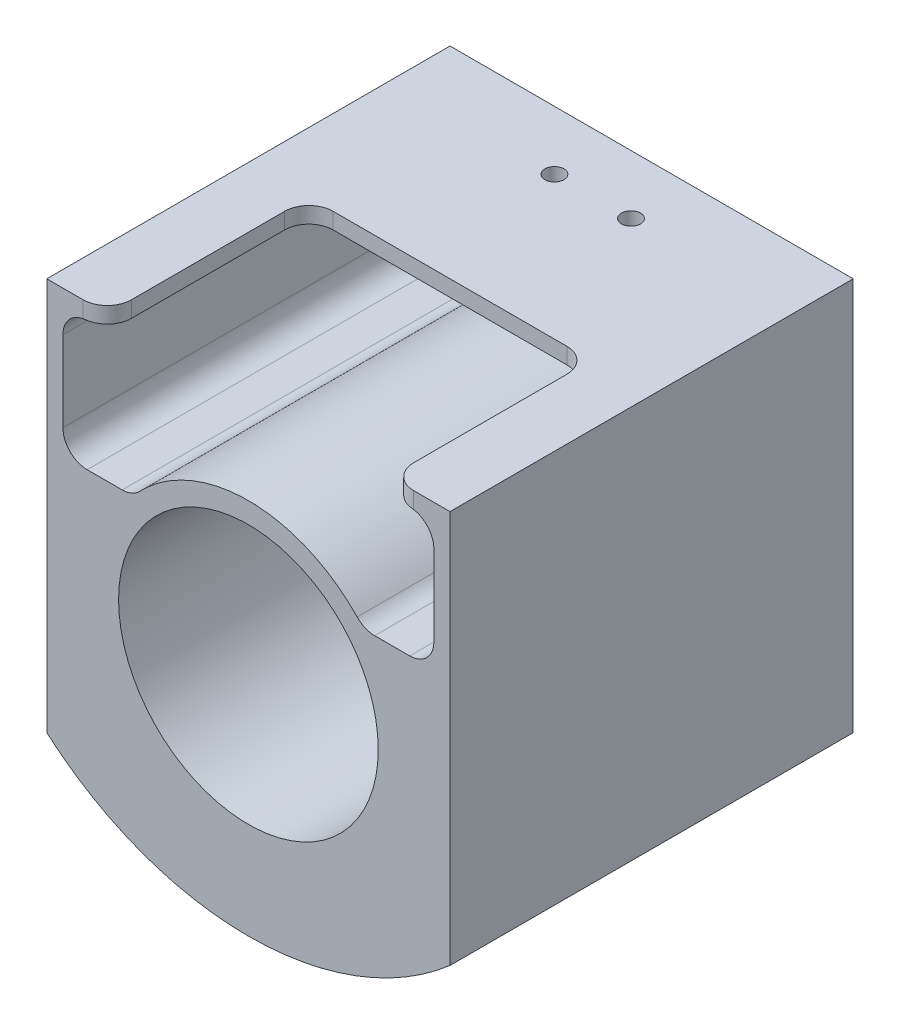
SolidWorks part; units mm, degrees
ref_plane "Front Plane" through (0, 0, 0) normal (0, 0, 1) x (1, 0, 0)
ref_plane "Top Plane" through (0, 0, 0) normal (0, 1, 0) x (1, 0, 0)
ref_plane "Right Plane" through (0, 0, 0) normal (1, 0, 0) x (0, 0, -1)
sketch "Sketch1" plane through (0, 0, 0) normal (0, 0, 1) x (1, 0, 0)
  line L1 (0, 0) -> (0, -38.1) construction
  line L2 (-25, 0) -> (-25, -28.7508)
  line L3 (25, 0) -> (25, -28.7508)
  line L4 (-25, 0) -> (-25, 20)
  line L5 (-25, 20) -> (25, 20)
  line L6 (25, 20) -> (25, 0)
  arc A0 (-25, -28.7508) -> (25, -28.7508) centre (0, 0) ccw
  dimension "D1" = 76.2
  dimension "D2" = 50
  dimension "D3" = 20
extrude "Boss-Extrude2" add sketch "Sketch1" along normal blind 50
sketch "Sketch2" plane through (0, 0, 50) normal (0, 0, 1) x (1, 0, 0)
  line L6 (0, 6.1) -> (0, -26.1) construction
  circle A0 centre (0, -10) radius 16.1
  dimension "D2" = 32.2
  dimension "D1" = 10
extrude "Cut-Extrude1" cut sketch "Sketch2" against normal through all both
sketch "Sketch4" plane through (0, 0, 50) normal (0, 0, 1) x (1, 0, 0)
  line L0 (-23, 18) -> (23, 18)
  line L3 (0, 20) -> (0, 6.1) construction
  line L4 (25, 20) -> (-25, 20) construction
  line L5 (23, 2) -> (14.3178, 2)
  line L6 (-23, 18) -> (-23, 2)
  line L7 (-23, 2) -> (-14.3178, 2)
  line L8 (-25, 20) -> (-25, -28.7508) construction
  line L9 (23, 18) -> (23, 2)
  circle A2 centre (0, -10) radius 16.1 construction
  arc A3 (14.3178, 2) -> (-14.3178, 2) centre (0, -10) ccw
  point P2 (0, 13.05)
  point P14 (0, 18)
  dimension "D1" = 37.3631
  dimension "D2" = 2
  dimension "D3" = 2
  dimension "D4" = 16
extrude "Cut-Extrude3" cut sketch "Sketch4" against normal through all
fillet "Fillet1" radius 3 6 edges at (23, 18, 25) (23, 2, 25) (14.3178, 2, 25) (-14.3178, 2, 25) (-23, 2, 25) (-23, 18, 25)
sketch "Sketch5" plane through (0, 20, 0) normal (0, 1, 0) x (1, 0, 0)
  line L0 (25, -50) -> (-25, -50) construction
  line L1 (-17.5, -50) -> (17.5, -50)
  line L2 (-17.5, -50) -> (-17.5, -25)
  line L3 (-17.5, -25) -> (17.5, -25)
  line L4 (17.5, -50) -> (17.5, -25)
  line L5 (0, 0) -> (0, -50) construction
  dimension "D1" = 35
  dimension "D2" = 25
extrude "Cut-Extrude4" cut sketch "Sketch5" against normal blind 10
fillet "Fillet2" radius 3 4 edges at (17.5, 19, 50) (17.5, 19, 25) (-17.5, 19, 25) (-17.5, 19, 50)
ref_plane "Plane1" through (0, 0, 14) normal (0, 0, 1) x (1, 0, 0)
sketch "Sketch6" plane through (0, 0, 14) normal (0, 0, 1) x (1, 0, 0)
  circle A1 centre (0, -10) radius 16.1 construction
  circle A3 centre (0, -10) radius 9.5
  circle A4 centre (0, 3) radius 1.25
  circle A5 centre (13, -10) radius 1.25
  circle A6 centre (-13, -10) radius 1.25
  circle A7 centre (0, -23) radius 1.25
  circle A8 centre (0, -10) radius 16.1
  dimension "D1" = 19
  dimension "D6" = 2.5
  dimension "D7" = 32.2
  dimension "D2" = 13
  dimension "D3" = 13
  dimension "D4" = 13
  dimension "D5" = 13
extrude "Boss-Extrude3" add sketch "Sketch6" against normal blind 5
sketch "Sketch7" plane through (0, 0, 0) normal (1, 0, 0) x (0, 0, -1)
  circle A0 centre (-40, -32) radius 2.25
  circle A1 centre (-10, -32) radius 2.25
  dimension "D3" = 4.5
  dimension "D1" = 32
  dimension "D2" = 10
  dimension "D4" = 30
extrude "Cut-Extrude5" cut sketch "Sketch7" against normal through all both and the other way through all
sketch "Sketch8" plane through (0, 20, 0) normal (0, 1, 0) x (1, 0, 0)
  line L0 (0, 0) -> (0, -25) construction
  line L1 (25, 0) -> (-25, 0) construction
  line L2 (14.5, -25) -> (-14.5, -25) construction
  circle A0 centre (-4.75, -7.3) radius 1.175
  circle A1 centre (4.75, -7.3) radius 1.175
  dimension "D1" = 2.35
  dimension "D2" = 9.5
  dimension "D3" = 7.3
extrude "Cut-Extrude6" cut sketch "Sketch8" against normal up to next contours A0 | A1
